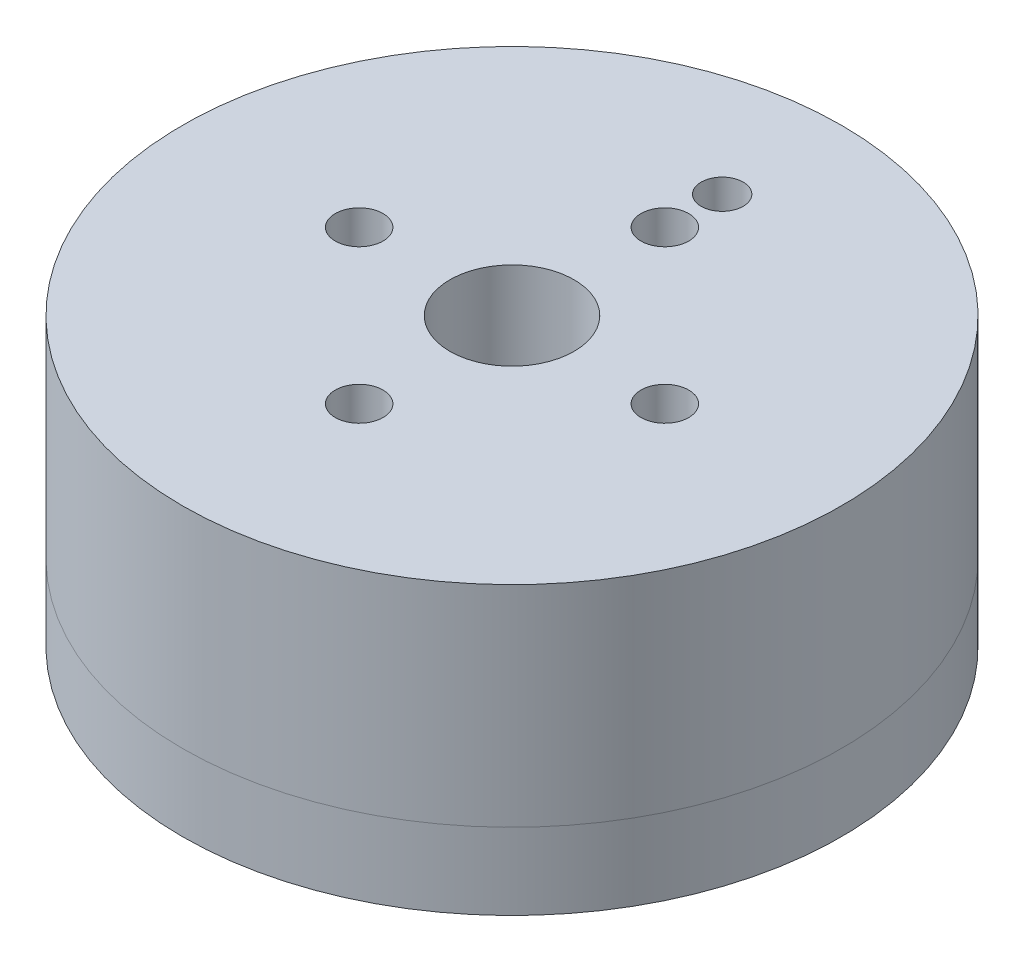
SolidWorks part; units mm, degrees
ref_plane "Front Plane" through (0, 0, 0) normal (0, 0, 1) x (1, 0, 0)
ref_plane "Top Plane" through (0, 0, 0) normal (0, 1, 0) x (1, 0, 0)
ref_plane "Right Plane" through (0, 0, 0) normal (1, 0, 0) x (0, 0, -1)
sketch "Sketch1" plane through (0, 0, 0) normal (0, 1, 0) x (1, 0, 0)
  circle A0 centre (0, 0) radius 17.25
  dimension "D1" = 34.5
extrude "Boss-Extrude1" add sketch "Sketch1" along normal blind 11
sketch "Sketch2" plane through (0, 11, 0) normal (0, 1, 0) x (1, 0, 0)
  circle A0 centre (0, 0) radius 8 construction
  circle A2 centre (0, 8) radius 1.25
  circle A3 centre (0, 11) radius 1.1
  circle A4 centre (8, 0) radius 1.25
  circle A5 centre (0, 0) radius 8 construction
  circle A6 centre (0, -8) radius 1.25
  circle A7 centre (0, 0) radius 8 construction
  circle A8 centre (-8, 0) radius 1.25
  circle A9 centre (0, 0) radius 8 construction
  point P8 (0, 0)
  point P20 (0, 0)
  dimension "D1" = 16
  dimension "D2" = 2.5
  dimension "D3" = 2.2
  dimension "D6" = 3
  dimension "D5" = 4
extrude "Cut-Extrude1" cut sketch "Sketch2" against normal blind 3
extrude "Boss-Extrude2" add sketch "Sketch1<2>" against normal blind 4 separate body
sketch "Sketch1<2>" plane through (0, 0, 0) normal (0, 1, 0) x (1, 0, 0) same geometry as "Sketch1"
sketch "Sketch4" plane through (0, -4, 0) normal (0, -1, 0) x (1, 0, 0)
  line L0 (-17.25, 0) -> (17.25, 0) construction
  line L2 (0, 17.25) -> (0, -17.25) construction
  line L3 (-6.7, 6.7) -> (6.7, 6.7) construction
  line L4 (-6.7, 6.7) -> (-6.7, -6.7) construction
  line L5 (-6.7, -6.7) -> (6.7, -6.7) construction
  line L6 (6.7, 6.7) -> (6.7, -6.7) construction
  line L7 (-6.7, 6.7) -> (6.7, -6.7) construction
  line L8 (-6.7, -6.7) -> (6.7, 6.7) construction
  circle A0 centre (0, 0) radius 17.25 construction
  circle A2 centre (-6.7, 6.7) radius 1.25
  circle A3 centre (6.7, 6.7) radius 1.25
  circle A4 centre (6.7, -6.7) radius 1.25
  circle A5 centre (-6.7, -6.7) radius 1.25
  circle A6 centre (13.1674, 0) radius 1.1
  point P7 (0, 0)
  point P15 (0, 0)
  dimension "D3" = 2.5
  dimension "D6" = 2.2
  dimension "D1" = 13.4
  dimension "D2" = 13.4
  dimension "D4" = 2
  dimension "D5" = 2
extrude "Cut-Extrude3" cut sketch "Sketch4" against normal blind 4
sketch "Sketch5" plane through (0, -4, 0) normal (0, -1, 0) x (1, 0, 0)
  circle A0 centre (0, 0) radius 5
  circle A1 centre (0, 0) radius 6
  circle A2 centre (0, 0) radius 2.7
  dimension "D1" = 10
  dimension "D2" = 12
  dimension "D3" = 5.4
extrude "Boss-Extrude3" add sketch "Sketch5" along normal blind 4.5 contours A0
extrude "Boss-Extrude4" add sketch "Sketch5<3>" against normal blind 2.5 from surface contours A1 A0 region at (-5.8303, -4, 0) starting at face at (0, -8.5, -5)
sketch "Sketch5<3>" plane through (0, -4, 0) normal (0, -1, 0) x (1, 0, 0) same geometry as "Sketch5"
extrude "Cut-Extrude4" cut sketch "Sketch5<5>" against normal up to surface (-2 mm away) from surface contours A2 up to face at (0, -6, -5) starting at face at (0, -8.5, -6)
sketch "Sketch5<5>" plane through (0, -4, 0) normal (0, -1, 0) x (1, 0, 0) same geometry as "Sketch5"
sketch "Sketch6" plane through (0, 0, 0) normal (0, 1, 0) x (1, 0, 0)
  circle A0 centre (0, 0) radius 3.25
  dimension "D1" = 6.5
extrude "Cut-Extrude5" cut sketch "Sketch6" along normal up to surface (11 mm away) and the other way up to surface (6 mm away) up to face at (0, 11, -9.9) other way up to face at (0, -6, -5)
fillet "Fillet1" radius 2 1 edges at (0, -6, -5) first distance on face at (0, -4, 5)
